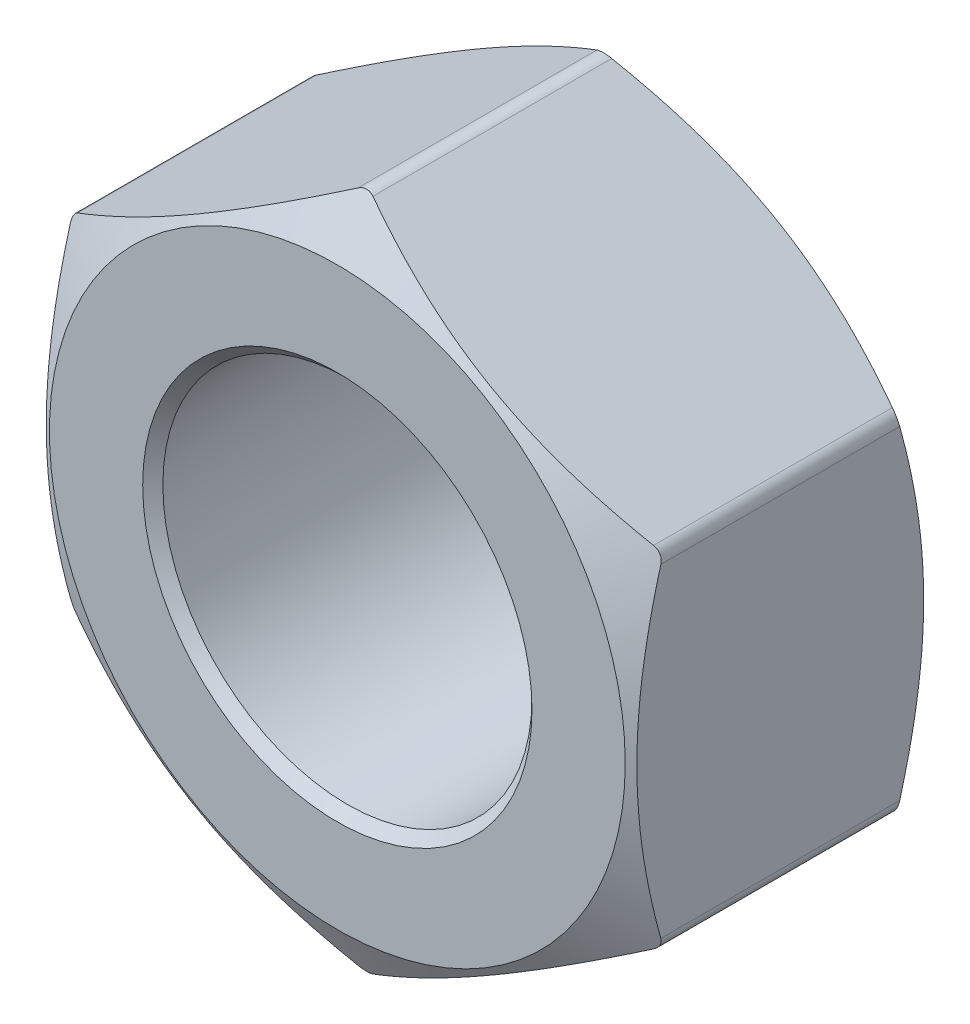
SolidWorks part; units mm, degrees
ref_plane "Front Plane" through (0, 0, 0) normal (0, 0, 1) x (1, 0, 0)
ref_plane "Top Plane" through (0, 0, 0) normal (0, 1, 0) x (1, 0, 0)
ref_plane "Right Plane" through (0, 0, 0) normal (1, 0, 0) x (0, 0, -1)
sketch "Sketch1" plane through (0, 0, 0) normal (1, 0, 0) x (0, 0, -1)
  line L0 (-2, 0) -> (2, 0) construction
  line L1 (-2, -4) -> (-2, 4) construction
  line L2 (2, -4) -> (2, 4) construction
  line L3 (-2, -2.5) -> (-2, 2.5) construction
  line L4 (-2.75, 2.5866) -> (-2.35, 1.8938) construction
  line L5 (-2.35, 1.8938) -> (-1.95, 2.5866) construction
  line L6 (-1.95, 2.5866) -> (-2.75, 2.5866) construction
  line L7 (-2.725, 2.5433) -> (-1.975, 2.5433) construction
  line L8 (-2.7, 2.5) -> (-2, 2.5) construction
  line L9 (-2.4, 1.9804) -> (-2.3, 1.9804) construction
  line L10 (-2.35, 1.9804) -> (-2.35, 1.8938) construction
  line L11 (-2.35, 2.5866) -> (-2.35, 2.5) construction
  line L12 (-2, 2.6366) -> (-1.8634, 2.5) construction
  point P4 (0, 0)
  point P7 (-2, 0)
  point P11 (2, 0)
  point P14 (-2, 0)
  point P26 (-2.35, 2.5433)
  point P27 (-2, -2.5)
  dimension "Height" = 4
  dimension "Width" = 8
  dimension "Thread Size" = 5
  dimension "D1" = 60
  dimension "Thread Pitch" = 0.8
  dimension "D2" = 0.1
  dimension "D3" = 45
sketch "Sketch2" plane through (0, 0, 0) normal (0, 0, 1) x (1, 0, 0)
  line L1 (0, 4.6188) -> (-4, 2.3094)
  line L2 (-4, 2.3094) -> (-4, -2.3094)
  line L3 (-4, -2.3094) -> (0, -4.6188)
  line L4 (0, -4.6188) -> (4, -2.3094)
  line L5 (4, -2.3094) -> (4, 2.3094)
  line L6 (4, 2.3094) -> (0, 4.6188)
  circle A0 centre (0, 0) radius 4 construction
  circle A1 centre (0, 0) radius 2.5
extrude "Boss-Extrude1" add sketch "Sketch2" along normal up to vertex (2 mm away) and the other way up to vertex (2 mm away) up to point (0, -4, 2) other way up to point (0, -4, -2)
sketch "Sketch3" plane through (0, 0, 2) normal (0, 0, 1) x (1, 0, 0)
  circle A0 centre (0, 0) radius 3.9
  dimension "D1" = 7.8
extrude "Cut-Extrude1" cut sketch "Sketch3" against normal through all draft 60 flip side to cut
fillet "Fillet1" radius 0.2 6 edges at (4, -2.3094, -0.2075) (0, -4.6188, -0.2075) (-4, -2.3094, -0.2075) (-4, 2.3094, -0.2075) (4, 2.3094, -0.2075) (0, 4.6188, -0.2075)
sketch "Sketch8" plane through (0, 0, 2) normal (0, 0, 1) x (1, 0, 0)
  circle A0 centre (0, 0) radius 2.6366
extrude "Cut-Extrude4" cut sketch "Sketch8" against normal through all draft 45
mirror "Mirror1" about plane through (0, 0, 0) normal (0, 0, 1) of "Cut-Extrude4", "Cut-Extrude1"
sketch "Sketch4" [suppressed] plane through (0, 0, 0) normal (1, 0, 0) x (0, 0, -1)
  line L1 (-2.725, 2.5433) -> (-2.4, 1.9804)
  line L2 (-2.4, 1.9804) -> (-2.3, 1.9804)
  line L3 (-2.3, 1.9804) -> (-1.975, 2.5433)
  line L4 (-2.725, 2.5433) -> (-1.975, 2.5433) construction
  line L5 (-2.725, 2.5433) -> (-1.975, 2.5433)
sketch "Sketch5" [suppressed] plane through (0, 0, 2) normal (0, 0, 1) x (1, 0, 0)
  circle A0 centre (0, 0) radius 2.5 construction
  circle A1 centre (0, 0) radius 2.5
curve "Helix/Spiral1" [suppressed] pitch 0.8 height 4.8 turns 6
sweep "Sweep1" [suppressed] add profiles "Sketch4" path "Helix/Spiral1"
sketch "Sketch6" [suppressed] plane through (0, 0, 2) normal (0, 0, 1) x (1, 0, 0)
  circle A0 centre (0, 0) radius 2.6366 construction
  circle A1 centre (0, 0) radius 2.6366
extrude "Cut-Extrude2" [suppressed] cut sketch "Sketch6" along normal through all and the other way through all draft 45
sketch "Sketch7" [suppressed] plane through (0, 0, -2) normal (0, 0, -1) x (-1, 0, 0)
  circle A1 centre (0, 0) radius 2.6366
  circle A2 centre (0, 0) radius 2.6366
  dimension "D1" = 0
extrude "Cut-Extrude3" [suppressed] cut sketch "Sketch7" along normal through all and the other way through all draft 45
equation "\"D2@Sketch1\"=\"Thread Pitch@Sketch1\"/8"
equation "\"D4@Helix/Spiral1\"=\"Thread Pitch@Sketch1\""
equation "\"D3@Helix/Spiral1\"=\"Height@Sketch1\"+\"Thread Pitch@Sketch1\""
equation "\"D1@Sketch3\"=\"Width@Sketch1\"*.975"
equation "\"D1@Fillet1\"=\"Width@Sketch1\"*.025"
